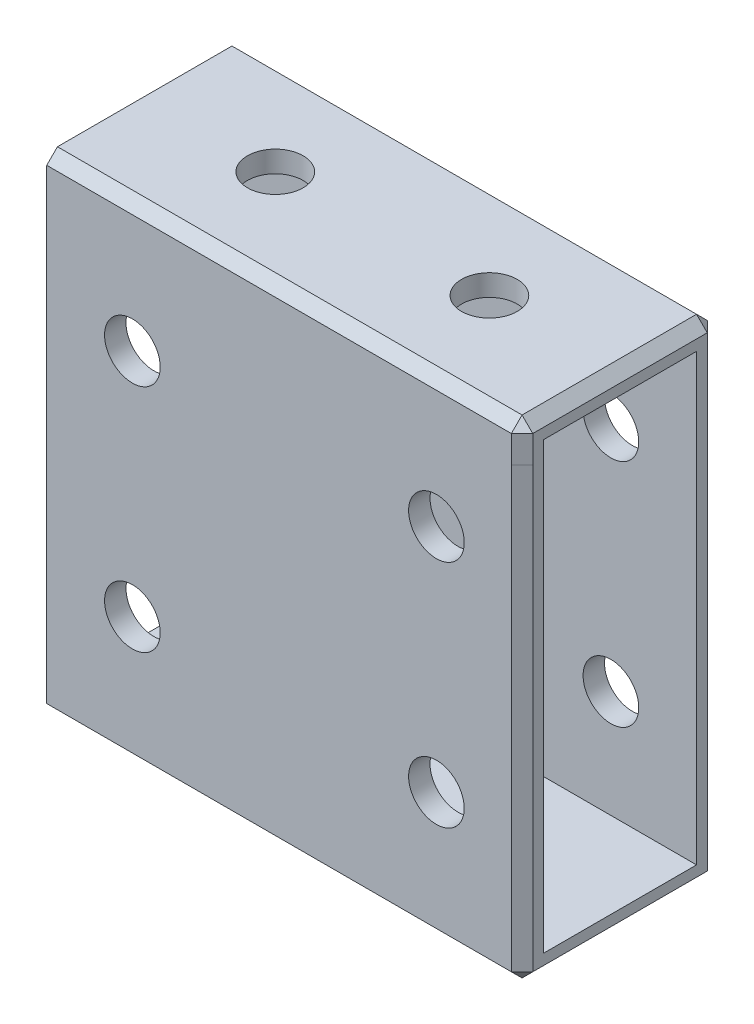
SolidWorks part; units mm, degrees
ref_plane "Front Plane" through (0, 0, 0) normal (0, 0, 1) x (1, 0, 0)
ref_plane "Top Plane" through (0, 0, 0) normal (0, 1, 0) x (1, 0, 0)
ref_plane "Right Plane" through (0, 0, 0) normal (1, 0, 0) x (0, 0, -1)
sketch "Sketch1" plane through (0, 0, 0) normal (0, 0, 1) x (1, 0, 0)
  line L0 (22.2, 40) -> (22.2, 0) construction
  line L1 (0, 0) -> (44.4, 0)
  line L2 (0, 0) -> (0, 40)
  line L3 (0, 40) -> (44.4, 40)
  line L4 (44.4, 0) -> (44.4, 40)
  line L5 (0, 0) -> (8, 0) construction
  line L6 (0, 0) -> (0, 8) construction
  line L10 (8, 29.9769) -> (8, 27.3769) construction
  line L11 (8, 19) -> (8, 8.4769) construction
  line L12 (8, 19) -> (10.573, 19) construction
  line L15 (10.573, 19) -> (10.573, 40) construction
  line L16 (8, 8.4769) -> (36.4, 8.4769) construction
  line L17 (36.4, 8.4769) -> (36.4, 29.9769) construction
  circle A0 centre (8, 8.4769) radius 2.6
  circle A1 centre (8, 29.9769) radius 2.6
  circle A2 centre (36.4, 29.9769) radius 2.6
  circle A3 centre (36.4, 8.4769) radius 2.6
  dimension "D5" = 5.2
  dimension "D6" = 5.2
  dimension "D7" = 5.2
  dimension "D8" = 5.2
  dimension "D1" = 44.4
  dimension "D2" = 40
  dimension "D3" = 21.5
  dimension "D4" = 21.5
  dimension "D9" = 21
  dimension "D10" = 8
  dimension "D11" = 8
extrude "Boss-Extrude1" add sketch "Sketch1" along normal blind 2
sketch "Sketch2" plane through (0, 40, 0) normal (0, 1, 0) x (1, 0, 0)
  line L0 (44.4, -2) -> (44.4, 0) construction
  line L1 (0, -2) -> (44.4, -2)
  line L2 (0, -2) -> (0, 16.3)
  line L3 (0, 16.3) -> (44.4, 16.3)
  line L4 (44.4, -2) -> (44.4, 16.3)
  dimension "D1" = 18.3
  dimension "D2" = 44.4
extrude "Boss-Extrude2" add sketch "Sketch2" along normal blind 2
pattern_linear "LPattern1" count 2 spacing 16.3 along (0, 0, -1) of "Boss-Extrude1"
sketch "Sketch3" plane through (0, 42, 0) normal (0, 1, 0) x (1, 0, 0)
  line L0 (22.2, 16.3) -> (22.2, -2) construction
  line L1 (44.4, 16.3) -> (0, 16.3) construction
  line L2 (0, -2) -> (44.4, -2) construction
  line L3 (22.2, 7.15) -> (12.2, 7.15) construction
  line L4 (22.2, 7.15) -> (32.2, 7.15) construction
  circle A0 centre (12.2, 7.15) radius 2.6
  circle A1 centre (32.2, 7.15) radius 2.6
  dimension "D3" = 5.2
  dimension "D4" = 5.2
  dimension "D1" = 10
  dimension "D2" = 10
extrude "Cut-Extrude1" cut sketch "Sketch3" against normal through all
chamfer "Chamfer1" distance 1 angle 45 11 edges at (22.2, 42, -16.3) (22.2, 42, 2) (0, 0, -15.3) (0, 0, 1) (22.2, 0, 2) (44.4, 0, 1) (44.4, 21, 2) (44.4, 42, -7.15) (44.4, 21, -16.3) (44.4, 0, -15.3) (22.2, 0, -16.3)
sketch "Sketch4" plane through (0, 0, 2) normal (0, 0, 1) x (1, 0, 0)
  line L3 (36.4, 8.4769) -> (36.4, 29.9769) construction
  line L4 (36.4, 19.2269) -> (1, 19.2269) construction
  line L5 (1, 41) -> (1, 1) construction
ref_plane "Plane1" through (0, 19.2269, 0) normal (0, 1, 0) x (1, 0, 0)
mirror "Mirror1" about plane through (0, 19.2269, 0) normal (0, 1, 0) of "LPattern1", "Boss-Extrude2", "Boss-Extrude1"
chamfer "Chamfer3" distance 1 angle 45 5 edges at (44.4, 17.4538, 2) (44.4, 17.4538, -16.3) (44.4, -3.5462, -7.15) (22.2, -3.5462, 2) (22.2, -3.5462, -16.3)
